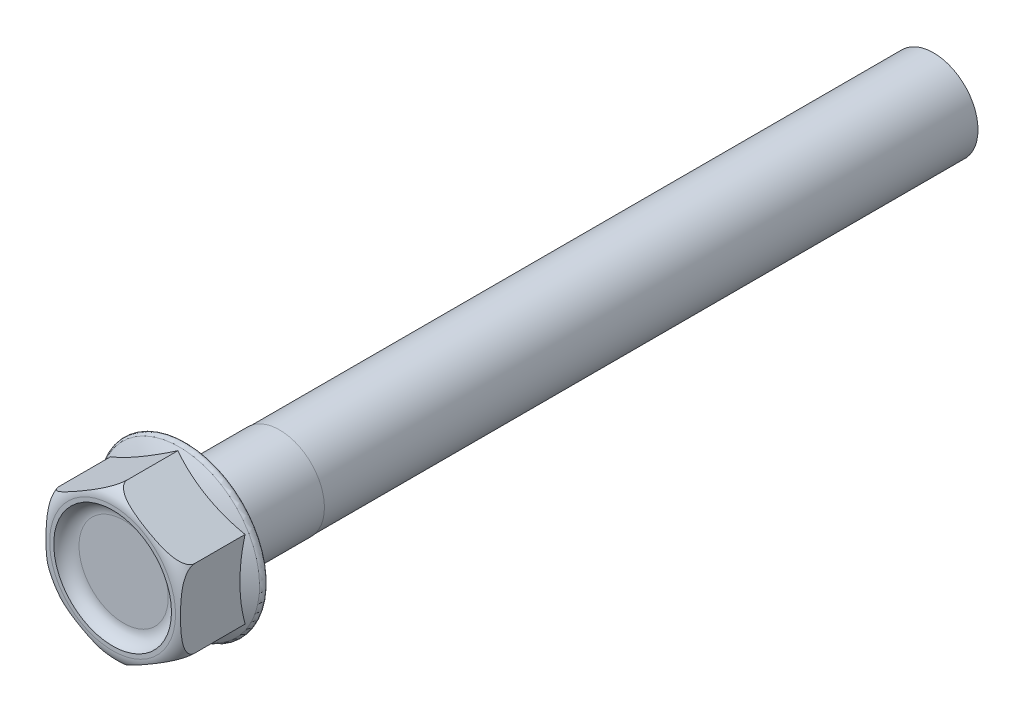
SolidWorks part; units mm, degrees
note: '?' marks a value the reader was unsure of.
extrude "Shank" add sketch "Shank Sketch" against normal blind 101.6
sketch "Shank Sketch" plane through (0, 0, 0) normal (0, 0, 1) x (1, 0, 0)
  line L0 (50, 0) -> (-50, 0) construction
  line L1 (0, -50) -> (0, 50) construction
  circle A0 centre (0, 0) radius 6.096
  dimension "Shank diameter" = 12.192
extrude "Head" add sketch "Head Sketch" along normal blind 10
sketch "Head Sketch" plane through (0, 0, 0) normal (0, 0, 1) x (1, 0, 0)
  line L0 (0, 10.5586) -> (9.144, 5.2793)
  line L1 (9.144, 5.2793) -> (9.144, -5.2793)
  line L2 (9.144, -5.2793) -> (0, -10.5586)
  line L3 (0, -10.5586) -> (-9.144, -5.2793)
  line L4 (-9.144, -5.2793) -> (-9.144, 5.2793)
  line L5 (-9.144, 5.2793) -> (0, 10.5586)
  line L6 (9.144, 5.2793) -> (-9.144, -5.2793) construction
  line L7 (0, 10.5586) -> (0, -10.5586) construction
  line L8 (-9.144, 5.2793) -> (9.144, -5.2793) construction
  point P0 (0, 0)
  dimension "D1" = 60
  dimension "D2" = 60
  dimension "Width across flats" = 18.288
ref_plane "Plane1" through (0, 0, 0) normal (0, 0, 1) x (1, 0, 0)
ref_plane "Plane2" through (0, 0, 0) normal (0, 1, 0) x (-1, 0, 0)
ref_plane "Plane3" through (0, 0, 0) normal (1, 0, 0) x (0, 0, -1)
other "Configuration Table"
sketch "Sketch3" plane through (0, 0, 0) normal (0, 1, 0) x (-1, 0, 0)
  line L0 (0, 0) -> (0, 7.62) construction
  line L1 (0, -101.6) -> (0, 0) construction
  line L4 (-10.668, 0) -> (0, 0)
  line L5 (0, 0) -> (0, 3.81)
  arc A0 (0, 3.81) -> (-10.9143, 0.9351) centre (0, -18.3452) ccw
  arc A1 (-10.668, 0) -> (-10.9143, 0.9351) centre (-10.668, 0.5) cw
  dimension "D1" = 0.5
  dimension "D2" = 21.336
  dimension "D3" = 3.81
revolve "Flange" add sketch "Sketch3" angle 360 about L0
ref_axis "Axis1" through (0, 0, -151.6) along (0, 0, 1)?
sketch "Sketch5" plane through (0, 0, 0) normal (1, 0, 0) x (0, 0, -1)
  line L0 (-10, -8.5586) -> (-10, -10.5586)
  line L1 (-10, -10.5586) -> (-8, -10.5586)
  line L2 (-10, -10.5586) -> (-1.1322, -10.5586) construction
  line L3 (-10, -10.5586) -> (-10, -5.2793) construction
  line L5 (-15.0856, 0) -> (-8.1394, 0) construction
  line L6 (50, 0) -> (-50, 0) construction
  arc A0 (-10, -8.5586) -> (-8, -10.5586) centre (-8, -8.5586) ccw
  dimension "D1" = 2
revolve "Head Trim" cut sketch "Sketch5" angle 360 about L5
sketch "Sketch6" plane through (0, 0, 10) normal (0, 0, 1) x (1, 0, 0)
  circle A3 centre (0, 0) radius 8.001
  dimension "D1" = 16.002
extrude "Head Cut" cut sketch "Sketch6" against normal blind 1.5
fillet "Fillet1" radius 2 1 edges at (8.001, 0, 8.5)
fillet "Fillet2" radius 0.5 1 edges at (6.096, 0, 0)
sketch "Thread End" plane through (0, 0, 0) normal (1, 0, 0) x (0, 0, -1)
  line L0 (12.7, 6.096) -> (12.7, 6.046)
  line L1 (101.6, 6.096) -> (0.5, 6.096) construction
  line L2 (12.7, 6.046) -> (101.6, 6.046)
  line L3 (101.6, 6.096) -> (12.7, 6.096)
  line L4 (21.5519, 0) -> (27.4271, 0) construction
  line L5 (101.6, 0) -> (0.5, 0) construction
  line L6 (101.6, -6.096) -> (101.6, 6.096) construction
  line L7 (101.6, 6.046) -> (101.6, 6.096)
  dimension "D1" = 0.05
  dimension "Length of thread" = 88.9
revolve "Thread Cut" cut sketch "Thread End" angle 360 about L4
cosmetic thread "Cosmetic Thread2" parameters "D2"=11
equation "\"D1@Sketch6\" = \"Width across flats@Head Sketch\"*7/8"
